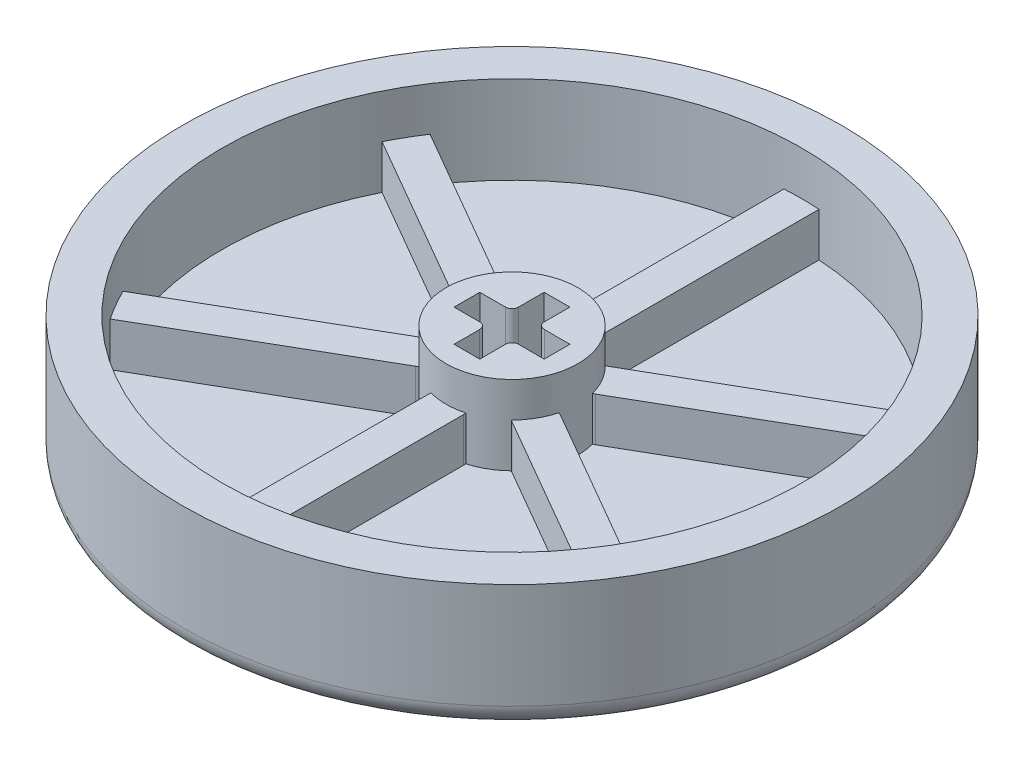
SolidWorks part; units mm, degrees
ref_plane "Front Plane" through (0, 0, 0) normal (0, 0, 1) x (1, 0, 0)
ref_plane "Top Plane" through (0, 0, 0) normal (0, 1, 0) x (1, 0, 0)
ref_plane "Right Plane" through (0, 0, 0) normal (1, 0, 0) x (0, 0, -1)
sketch "Sketch1" plane through (0, 0, 0) normal (0, 1, 0) x (1, 0, 0)
  circle A0 centre (0, 0) radius 15
  dimension "D1" = 30
extrude "button top" add sketch "Sketch1" along normal blind 1.8
sketch "Sketch2" plane through (0, 1.8, 0) normal (0, 1, 0) x (1, 0, 0)
  circle A3 centre (0, 0) radius 15
  circle A4 centre (0, 0) radius 15 construction
  circle A5 centre (0, 0) radius 13.2
  dimension "D1" = 1.8
extrude "button walls" add sketch "Sketch2" along normal blind 4
sketch "Sketch3" plane through (0, 1.8, 0) normal (0, 1, 0) x (1, 0, 0)
  line L0 (0, -2.05) -> (0, 2.05) construction
  line L1 (-2.05, 0) -> (2.05, 0) construction
  line L2 (-0.585, 0.885) -> (-0.585, 2.05)
  line L3 (-0.585, -2.05) -> (0.585, -2.05)
  line L4 (-0.585, -2.05) -> (-0.585, -0.885)
  line L5 (-0.585, 2.05) -> (0.585, 2.05)
  line L6 (0.585, -2.05) -> (0.585, -0.885)
  line L7 (-0.585, -2.05) -> (0.585, 2.05) construction
  line L8 (-0.585, 2.05) -> (0.585, -2.05) construction
  line L9 (-2.05, -0.585) -> (-0.885, -0.585)
  line L10 (-2.05, -0.585) -> (-2.05, 0.585)
  line L11 (-2.05, 0.585) -> (-0.885, 0.585)
  line L12 (2.05, -0.585) -> (2.05, 0.585)
  line L13 (-2.05, -0.585) -> (2.05, 0.585) construction
  line L14 (-2.05, 0.585) -> (2.05, -0.585) construction
  line L15 (0.885, 0.585) -> (2.05, 0.585)
  line L16 (0.585, 0.885) -> (0.585, 2.05)
  line L17 (0.885, -0.585) -> (2.05, -0.585)
  circle A0 centre (0, 0) radius 3
  arc A1 (-0.585, -0.885) -> (-0.885, -0.585) centre (-0.885, -0.885) ccw
  arc A2 (0.585, -0.885) -> (0.885, -0.585) centre (0.885, -0.885) cw
  arc A3 (0.885, 0.585) -> (0.585, 0.885) centre (0.885, 0.885) cw
  arc A4 (-0.585, 0.885) -> (-0.885, 0.585) centre (-0.885, 0.885) cw
  point P6 (0, 0)
  point P9 (0, 0)
  point P22 (2.05, 0)
  point P24 (0, 2.05)
  point P29 (0.585, -0.585)
  point P32 (0.585, 0.585)
  dimension "D1" = 6
  dimension "D4" = 0.3
  dimension "D2" = 4.1
  dimension "D3" = 1.17
extrude "stem housing" add sketch "Sketch3" along normal blind 3.6
sketch "Sketch4" plane through (0, 1.8, 0) normal (0, 1, 0) x (1, 0, 0)
  line L0 (0, 3) -> (0, 13.2) construction
  line L1 (-0.8, 3) -> (-0.8, 13.2)
  line L2 (0.8, 3) -> (0.8, 13.2)
  line L3 (2.5981, 1.5) -> (11.4315, 6.6) construction
  line L4 (2.1981, 2.1928) -> (11.0315, 7.2928)
  line L5 (2.9981, 0.8072) -> (11.8315, 5.9072)
  line L6 (2.5981, -1.5) -> (11.4315, -6.6) construction
  line L7 (2.9981, -0.8072) -> (11.8315, -5.9072)
  line L8 (2.1981, -2.1928) -> (11.0315, -7.2928)
  line L9 (0, -3) -> (0, -13.2) construction
  line L10 (0.8, -3) -> (0.8, -13.2)
  line L11 (-0.8, -3) -> (-0.8, -13.2)
  line L12 (-2.5981, -1.5) -> (-11.4315, -6.6) construction
  line L13 (-2.1981, -2.1928) -> (-11.0315, -7.2928)
  line L14 (-2.9981, -0.8072) -> (-11.8315, -5.9072)
  line L15 (-2.5981, 1.5) -> (-11.4315, 6.6) construction
  line L16 (-2.9981, 0.8072) -> (-11.8315, 5.9072)
  line L17 (-2.1981, 2.1928) -> (-11.0315, 7.2928)
  circle A0 centre (0, 0) radius 3 construction
  circle A1 centre (0, 0) radius 3 construction
  circle A2 centre (0, 0) radius 13.2 construction
  arc A3 (-0.8, 3) -> (0.8, 3) centre (0, 3) ccw
  arc A4 (0.8, 13.2) -> (-0.8, 13.2) centre (0, 13.2) ccw
  arc A5 (2.1981, 2.1928) -> (2.9981, 0.8072) centre (2.5981, 1.5) ccw
  arc A6 (11.8315, 5.9072) -> (11.0315, 7.2928) centre (11.4315, 6.6) ccw
  arc A7 (2.9981, -0.8072) -> (2.1981, -2.1928) centre (2.5981, -1.5) ccw
  arc A8 (11.0315, -7.2928) -> (11.8315, -5.9072) centre (11.4315, -6.6) ccw
  arc A9 (0.8, -3) -> (-0.8, -3) centre (0, -3) ccw
  arc A10 (-0.8, -13.2) -> (0.8, -13.2) centre (0, -13.2) ccw
  arc A11 (-2.1981, -2.1928) -> (-2.9981, -0.8072) centre (-2.5981, -1.5) ccw
  arc A12 (-11.8315, -5.9072) -> (-11.0315, -7.2928) centre (-11.4315, -6.6) ccw
  arc A13 (-2.9981, 0.8072) -> (-2.1981, 2.1928) centre (-2.5981, 1.5) ccw
  arc A14 (-11.0315, 7.2928) -> (-11.8315, 5.9072) centre (-11.4315, 6.6) ccw
  point P9 (0, 8.1)
  point P18 (7.0148, 4.05)
  point P25 (7.0148, -4.05)
  point P32 (0, -8.1)
  point P39 (-7.0148, -4.05)
  point P46 (-7.0148, 4.05)
  point P51 (0, 0)
  dimension "D1" = 1.6
  dimension "D2" = 6
extrude "Boss-Extrude4" add sketch "Sketch4" along normal blind 2
fillet "Fillet1" radius 1 1 edges at (0, 0, 15)
